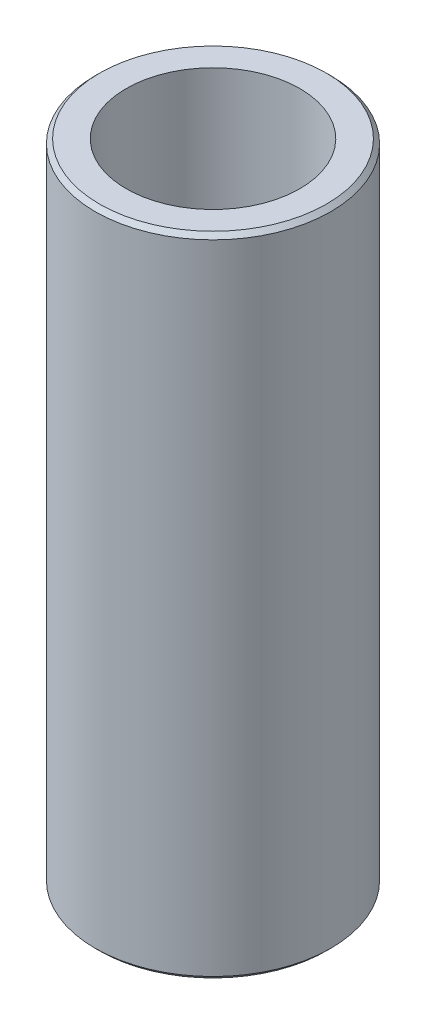
SolidWorks part; units mm, degrees
ref_plane "Front Plane" through (0, 0, 0) normal (0, 0, 1) x (1, 0, 0)
ref_plane "Top Plane" through (0, 0, 0) normal (0, 1, 0) x (1, 0, 0)
ref_plane "Right Plane" through (0, 0, 0) normal (1, 0, 0) x (0, 0, -1)
sketch "Sketch1" plane through (0, 0, 0) normal (0, 1, 0) x (1, 0, 0)
  circle A0 centre (0, 0) radius 40
  dimension "SHAFT_OD" = 80
extrude "Boss-Extrude1" add sketch "Sketch1" along normal blind 219.5541
sketch "Sketch2" plane through (0, 0, 0) normal (0, 1, 0) x (1, 0, 0)
  circle A0 centre (0, 0) radius 29.4789
  dimension "BORE_D" = 58.9577
extrude "Cut-Extrude1" cut sketch "Sketch2" along normal through all
chamfer "Chamfer1" distance 1.4853 angle 45 2 edges at (0, 219.5541, 40) (0, 0, 40)
